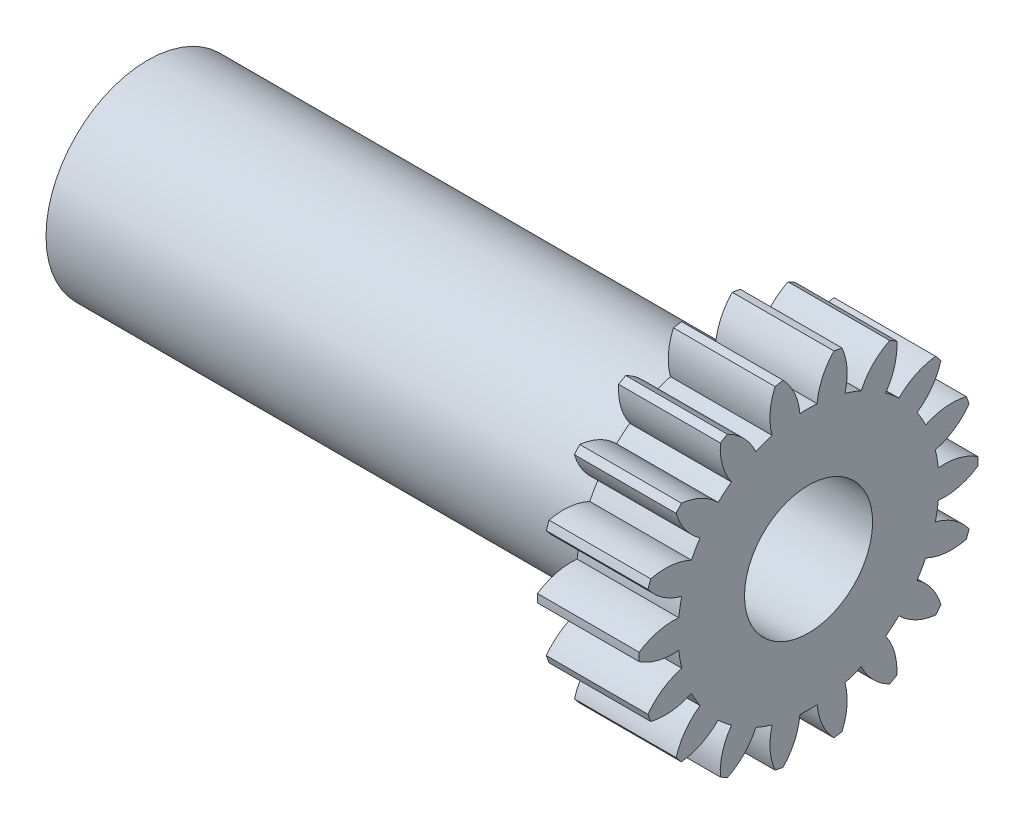
SolidWorks part; units mm, degrees
material "PET"
ref_plane "Plane1" through (0, 0, 0) normal (0, 0, 1) x (1, 0, 0)
ref_plane "Plane2" through (0, 0, 0) normal (0, 1, 0) x (1, 0, 0)
ref_plane "Plane3" through (0, 0, 0) normal (1, 0, 0) x (0, 0, -1)
sketch "HoldingSke" plane through (0, 0, 0) normal (0, 1, 0) x (1, 0, 0)
  line L0 (0, 0) -> (1159.5281, -376.7535)
  line L1 (-15, 0) -> (100, 0) construction
  line L2 (0, 0) -> (-2.1039, 2.3779)
  line L3 (0, 0) -> (-11.863, 4.5341)
  line L4 (0, 0) -> (8.2133, 2.6687)
  line L5 (0, 0) -> (-47.5972, -17.7524)
  line L6 (0, 0) -> (-2.632, -1.7758)
  line L7 (-2.1039, 2.3779) -> (8.8308, 51.9871)
  line L8 (-76.2, 54.61) -> (-75.184, 54.61)
  line L9 (-71.009, 38.7566) -> (-53.1078, 45.2721)
  line L10 (-76.2, 71.12) -> (104.1128, 71.12)
  line L11 (0, 0) -> (-3.175, 0)
  line L12 (-76.2, 101.6) -> (-76.1787, 101.6)
  line L13 (24.9733, 27.94) -> (52.9518, 28.4284)
  line L14 (24.9733, 27.94) -> (25.0241, 27.9398)
  line L15 (24.9733, 27.94) -> (100.4021, 29.52)
  circle A0 centre (0, 0) radius 0.3969
  circle A1 centre (0, 0) radius 4.0767
  circle A2 centre (0, 0) radius 38.1
  circle A3 centre (0, 0) radius 0.3969
  dimension "MHD" = 8.1534
  dimension "Hub_dia" = 76.2
  dimension "Bore" = 0.7937
  dimension "MBD" = 0.7937
  dimension "Num_teeth" = 18
  dimension "Pitch" = 1219.2
  dimension "Overall_len" = 50.8
  dimension "Show_teeth" = 18
  dimension "Thickness" = 3.175
  dimension "OAL" = 50.8001
  dimension "T_dim" = 1.016
  dimension "Ap" = 20
  dimension "H" = 19.05
  dimension "Pitch_radius" = 180.3128
  dimension "Width" = 3.175
  dimension "Backlash" = 0.0213
  dimension "Addendum_fac" = 1
  dimension "Dedendum_fac" = 1.2
  dimension "Clearance_fac" = 0.2
  dimension "Dedendum_add" = 0.0508
sketch "BasProSke" plane through (0, 0, 0) normal (0, 1, 0) x (1, 0, 0)
  line L0 (-10, 0) -> (60, 0) construction
  line L1 (0, 0) -> (0, 5.2917)
  line L2 (0, 0) -> (3.175, 0)
  line L3 (3.175, 0) -> (3.175, 5.2917)
  line L4 (3.175, 5.2917) -> (0, 5.2917)
  dimension "Thickness" = 3.175
  dimension "Diameter" = 10.5833
revolve "Base-Revolve" add sketch "BasProSke" angle 360 about L0
sketch "TooCutSke" plane through (0, 0, 0) normal (1, 0, 0) x (0, 0, -1)
  line L1 (0, 0) -> (0, 107) construction
  line L2 (0, 0) -> (-0.4524, 4.741) construction
  line L3 (0, 0) -> (-1.6488, 9.3507) construction
  line L4 (-0.4524, 4.741) -> (-0.8244, 4.6754) construction
  arc A0 (0.27, 4.0677) -> (-0.27, 4.0677) centre (0, 0) ccw
  arc A1 (0.8145, 5.2543) -> (-0.8145, 5.2543) centre (0, 0) ccw
  circle A2 centre (0, 0) radius 4.7625 construction
  circle A3 centre (0, 0) radius 4.4753 construction
  arc A4 (-0.27, 4.0677) -> (-0.8145, 5.2543) centre (-2.1688, 3.9146) ccw
  arc A5 (0.8145, 5.2543) -> (0.27, 4.0677) centre (2.1688, 3.9146) ccw
  dimension "Root_dia" = 8.1534
  dimension "Overcut_dia" = 10.6341
  dimension "Pitch_dia" = 9.525
  dimension "Base_dia" = 8.9506
  dimension "Flank_rad" = 1.905
  dimension "Half_ang" = 10
  dimension "Half_CT" = 0.3777
extrude "ToothCut" cut sketch "TooCutSke" along normal through all
fillet "Breaks" [suppressed] radius 0.0106 tangent propagation no
fillet "RootFillets" [suppressed] radius 0.1566
pattern_circular "TeethCuts" count 18 every 20 about axis through (-10, 0, 0) along (1, 0, 0) of "ToothCut", "RootFillets", "Breaks"
sketch "HubNeaOneSke" plane through (0, 0, 0) normal (-1, 0, 0) x (0, 0, 1)
  circle A0 centre (0, 0) radius 4.0767
  dimension "Diameter" = 8.1534
extrude "HubNearOne" [suppressed] add sketch "HubNeaOneSke" along normal blind 47.6251
sketch "HubNeaBotSke" plane through (0, 0, 0) normal (-1, 0, 0) x (0, 0, 1)
  circle A0 centre (0, 0) radius 4.0767
  dimension "Diameter" = 8.1534
extrude "HubNearBoth" [suppressed] add sketch "HubNeaBotSke" along normal blind 23.8125
ref_plane "FarPln" through (3.175, 0, 0) normal (1, 0, 0) x (0, 0, -1)
sketch "HubFarSke" plane through (3.175, 0, 0) normal (1, 0, 0) x (0, 0, -1)
  circle A0 centre (0, 0) radius 4.0767
  dimension "Diameter" = 8.1534
extrude "HubFar" [suppressed] add sketch "HubFarSke" along normal blind 23.8125
sketch "BorSke" plane through (0, 0, 0) normal (1, 0, 0) x (0, 0, -1)
  circle A0 centre (0, 0) radius 0.3969
  dimension "Diameter" = 0.7937
extrude "Bore" [suppressed] cut sketch "BorSke" along normal mid plane 101.6001
sketch "KeySke" plane through (0, 0, 0) normal (1, 0, 0) x (0, 0, -1)
  line L0 (-0.127, 0) -> (-0.127, 0.6191)
  line L1 (-0.127, 0.6191) -> (0.127, 0.6191)
  line L2 (0.127, 0.6191) -> (0.127, 0)
  line L3 (0, 0) -> (0, 34) construction
  line L4 (-0.127, 0) -> (0.127, 0)
  dimension "Offset" = 0.6191
  dimension "Width" = 0.254
extrude "Keyway" [suppressed] cut sketch "KeySke" along normal mid plane 101.6001
pattern_circular "Keyway2" [suppressed] count 2 every 90 about axis through (-10, 0, 0) along (1, 0, 0) reverse direction yes
sketch "Sketch1" [suppressed] plane through (0, 0, 0) normal (-1, 0, 0) x (0, 0, 1)
  circle A0 centre (0, 0) radius 2.7781
  dimension "D1" = 5.5562
extrude "Cut-Extrude2" [suppressed] cut sketch "Sketch1" against normal offset from surface (1.5875 mm away) 1.5875
sketch "Sketch2" plane through (0, 0, 0) normal (-1, 0, 0) x (0, 0, 1)
  circle A0 centre (0, 0) radius 2
  circle A1 centre (0, 0) radius 3.175
  dimension "D1" = 4
  dimension "D2" = 6.35
extrude "Cut-Extrude3" cut sketch "Sketch2" against normal through all contours A0 region at (0, 0, 0)
extrude "Boss-Extrude1" add sketch "Sketch2<3>" along normal blind 17.4625
sketch "Sketch2<3>" plane through (0, 0, 0) normal (-1, 0, 0) x (0, 0, 1) same geometry as "Sketch2"
ref_plane "Plane4" through (1.5875, 0, 0) normal (-1, 0, 0) x (0, 0, 1)
sketch "Sketch3" plane through (1.5875, 0, 0) normal (-1, 0, 0) x (0, 0, 1)
  circle A0 centre (0, 0) radius 4.7625
  dimension "D1" = 9.525
equation "' \"Pitch@HoldingSke\" = 4"
equation "' \"Num_teeth@HoldingSke\" = 12"
equation "' \"Ap@HoldingSke\" =  20"
equation "' \"Ap@HoldingSke\" = 20"
equation "' \"Width@HoldingSke\" = 0.5"
equation "' \"Hub_dia@HoldingSke\"= 1"
equation "' \"Hub_dia@HoldingSke\" = 1"
equation "' \"Overall_len@HoldingSke\" = 1.0"
equation "' \"Bore@HoldingSke\" = 0.75"
equation "' \"T_dim@HoldingSke\" = 0.85"
equation "' \"Width@KeySke\" = 0.25"
equation "' \"Show_teeth@HoldingSke\" = 13"
equation "' \"Backlash@HoldingSke\" = 0.009"
equation "' \"Addendum_fac@HoldingSke\" = 1.0"
equation "' \"Dedendum_fac@HoldingSke\" = 1.25"
equation "' \"Dedendum_add@HoldingSke\" = 0.00005"
equation "' \"Clearance_fac@HoldingSke\" = 0.25"
equation "' \"Pitch@HoldingSke\" = 0.5"
equation "' \"Num_teeth@HoldingSke\" = 23"
equation "' \"Show_teeth@HoldingSke\" = 23"
equation "' \"Backlash@HoldingSke\" = 0.0375"
equation "\"Overcut_dia@TooCutSke\" = (\"Num_teeth@HoldingSke\" + 2 * \"Addendum_fac@HoldingSke\") / \"Pitch@HoldingSke\" + 0.002"
equation "\"Pitch_dia@TooCutSke\" = \"Num_teeth@HoldingSke\" / \"Pitch@HoldingSke\""
equation "\"Base_dia@TooCutSke\" = \"Num_teeth@HoldingSke\" / \"Pitch@HoldingSke\" * cos((\"Ap@HoldingSke\"  * 3.14159265 / 180))"
equation "\"Root_dia@TooCutSke\" = (\"Num_teeth@HoldingSke\" + 2) / \"Pitch@HoldingSke\" - 2 * (\"Addendum_fac@HoldingSke\" + \"Dedendum_fac@HoldingSke\") / \"Pitch@HoldingSke\" - \"Dedendum_add@HoldingSke\" * 2"
equation "\"Half_ang@TooCutSke\" = 180 / \"Num_teeth@HoldingSke\""
equation "\"Half_CT@TooCutSke\" = \"Num_teeth@HoldingSke\" / \"Pitch@HoldingSke\" * sin((3.14159265 / 2 / \"Num_teeth@HoldingSke\")) / 2 - 7 * \"Backlash@HoldingSke\" / 4"
equation "\"Flank_rad@TooCutSke\" = \"Num_teeth@HoldingSke\" / \"Pitch@HoldingSke\" / 5"
equation "\"Radius@RootFillets\" = \"Clearance_fac@HoldingSke\" / \"Pitch@HoldingSke\" + \"Dedendum_add@HoldingSke\""
equation "\"Break_rad@Breaks\" = 0.02 / \"Pitch@HoldingSke\""
equation "\"Thickness@HoldingSke\" = \"Width@HoldingSke\""
equation "\"OAL@HoldingSke\" = \"Thickness@HoldingSke\""
equation "\"MHD@HoldingSke\" = (\"Num_teeth@HoldingSke\" + 2) / \"Pitch@HoldingSke\" - 2 * (\"Addendum_fac@HoldingSke\" + \"Dedendum_fac@HoldingSke\")  / \"Pitch@HoldingSke\" - \"Dedendum_add@HoldingSke\" * 2"
equation "\"MBD@HoldingSke\" = (\"Num_teeth@HoldingSke\" + 2) / \"Pitch@HoldingSke\" - 2 * (\"Addendum_fac@HoldingSke\" + \"Dedendum_fac@HoldingSke\")  / \"Pitch@HoldingSke\" - \"Dedendum_add@HoldingSke\" * 2 - 0.002"
equation "\"MHD@HoldingSke\" = ((sgn( \"MHD@HoldingSke\" - \"Hub_dia@HoldingSke\" )-1)*( \"MHD@HoldingSke\" - \"Hub_dia@HoldingSke\" ))/-2+ \"Hub_dia@HoldingSke\""
equation "\"MBD@HoldingSke\" = ((sgn( \"MBD@HoldingSke\" - \"Bore@HoldingSke\" )-1)*( \"MBD@HoldingSke\" - \"Bore@HoldingSke\" ))/-2+ \"Bore@HoldingSke\""
equation "\"OAL@HoldingSke\" = ((sgn( \"OAL@HoldingSke\" - \"Overall_len@HoldingSke\" )+1)*( \"OAL@HoldingSke\" - \"Overall_len@HoldingSke\" ))/2 + \"Overall_len@HoldingSke\" + 0.000002"
equation "\"Num_teeth@TeethCuts\" = int( \"Show_teeth@HoldingSke\" ) + 1"
equation "\"Num_teeth@TeethCuts\" = ((sgn( \"Num_teeth@TeethCuts\" - \"Num_teeth@HoldingSke\" )-1)*( \"Num_teeth@TeethCuts\" - \"Num_teeth@HoldingSke\" ))/-2+ \"Num_teeth@HoldingSke\""
equation "\"Num_teeth@TeethCuts\" = ((sgn( \"Num_teeth@TeethCuts\" - 2.0)+1)*( \"Num_teeth@TeethCuts\" - 2.0))/2 +2.0"
equation "\"Angle@TeethCuts\" = 360.0 / \"Num_teeth@HoldingSke\""
equation "\"Diameter@BasProSke\" = (\"Num_teeth@HoldingSke\" + 2 * \"Addendum_fac@HoldingSke\") / \"Pitch@HoldingSke\""
equation "\"Thickness@BasProSke\"  = \"Thickness@HoldingSke\""
equation "' \"Fillet_rad@BasProSke\" =  \"Thickness@HoldingSke\" * 0.05"
equation "' \"Fillet_rad@BasProSke\" = \"Thickness@HoldingSke\" * 0.05"
equation "\"MHD@HoldingSke\" = ((sgn( \"MHD@HoldingSke\" - \"Root_dia@TooCutSke\" )-1)*( \"MHD@HoldingSke\" - \"Root_dia@TooCutSke\" ))/-2+ \"Root_dia@TooCutSke\""
equation "\"Diameter@HubNeaOneSke\" = \"MHD@HoldingSke\""
equation "\"Length@HubNearOne\" = \"OAL@HoldingSke\" - \"Thickness@BasProSke\""
equation "\"Diameter@HubNeaBotSke\" = \"MHD@HoldingSke\""
equation "\"Length@HubNearBoth\" = ( \"OAL@HoldingSke\" - \"Thickness@BasProSke\" ) / 2.0"
equation "\"Thickness@FarPln\" = \"Thickness@BasProSke\""
equation "\"Diameter@HubFarSke\" = \"MHD@HoldingSke\""
equation "\"Length@HubFar\" = ( \"OAL@HoldingSke\" - \"Thickness@BasProSke\" ) / 2.0"
equation "\"Diameter@BorSke\" = \"MBD@HoldingSke\""
equation "\"D1@Bore\" = \"OAL@HoldingSke\" * 2.0"
equation "\"D1@Keyway\" = \"OAL@HoldingSke\" * 2.0"
equation "\"Offset@KeySke\" = \"T_dim@HoldingSke\" - \"MBD@HoldingSke\" / 2.0"
